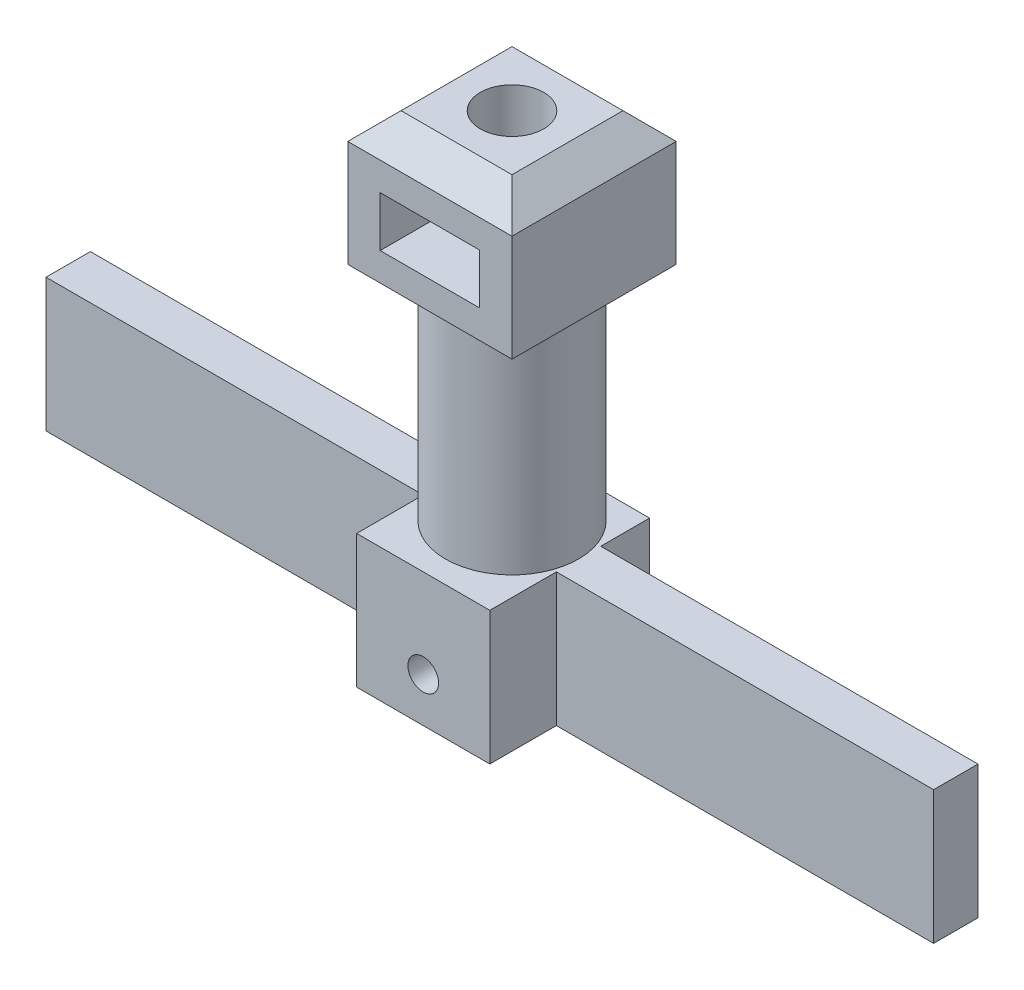
SolidWorks part; units mm, degrees
ref_plane "Front Plane" through (0, 0, 0) normal (0, 0, 1) x (1, 0, 0)
ref_plane "Top Plane" through (0, 0, 0) normal (0, 1, 0) x (1, 0, 0)
ref_plane "Right Plane" through (0, 0, 0) normal (1, 0, 0) x (0, 0, -1)
sketch "Sketch1" plane through (0, 0, 0) normal (0, 1, 0) x (1, 0, 0)
  line L1 (0, 0) -> (100, 0)
  line L2 (0, 0) -> (0, 10)
  line L3 (0, 10) -> (100, 10)
  line L4 (100, 0) -> (100, 10)
  dimension "D1" = 100
  dimension "D2" = 10
extrude "Boss-Extrude1" add sketch "Sketch1" along normal blind 15
sketch "Sketch2" plane through (0, 15, 0) normal (0, 1, 0) x (1, 0, 0)
  line L0 (100, 10) -> (0, 10) construction
  line L1 (100, 0) -> (100, 10) construction
  circle A0 centre (50, 5) radius 7.5
  dimension "D2" = 15
  dimension "D3" = 50
  dimension "D1" = 5
extrude "Boss-Extrude2" add sketch "Sketch2" along normal blind 20
sketch "Sketch3" plane through (0, 35, 0) normal (0, 1, 0) x (1, 0, 0)
  line L1 (40.75, 14.25) -> (59.25, 14.25)
  line L2 (40.75, 14.25) -> (40.75, -4.25)
  line L3 (40.75, -4.25) -> (59.25, -4.25)
  line L4 (59.25, 14.25) -> (59.25, -4.25)
  circle A0 centre (50, 5) radius 7.5 construction
  circle A1 centre (50, 5) radius 7.5 construction
  dimension "D4" = 9.25
  dimension "D1" = 18.5
  dimension "D2" = 18.5
  dimension "D3" = 9.25
extrude "Boss-Extrude3" add sketch "Sketch3" along normal blind 20
chamfer "Chamfer1" distance 3 angle 45 4 edges at (50, 55, -14.25) (59.25, 55, -5) (50, 55, 4.25) (40.75, 55, -5)
chamfer "Chamfer2" distance 5 angle 45 4 edges at (50, 35, -14.25) (40.75, 35, -5) (59.25, 35, -5) (50, 35, 4.25)
sketch "Sketch4" plane through (0, 0, 4.25) normal (0, 0, 1) x (1, 0, 0)
  line L0 (59.25, 52) -> (40.75, 52) construction
  line L1 (44.4, 48.825) -> (55.6, 48.825)
  line L2 (44.4, 48.825) -> (44.4, 43.175)
  line L3 (44.4, 43.175) -> (55.6, 43.175)
  line L4 (55.6, 48.825) -> (55.6, 43.175)
  line L5 (40.75, 40) -> (59.25, 40) construction
  line L6 (59.25, 52) -> (59.25, 40) construction
  line L7 (40.75, 52) -> (40.75, 40) construction
  dimension "D1" = 11.2
  dimension "D2" = 5.65
  dimension "D3" = 3.175
  dimension "D4" = 3.175
  dimension "D5" = 3.65
  dimension "D6" = 3.65
extrude "Cut-Extrude1" cut sketch "Sketch4" against normal through all
hole_wizard "1/4 Clearance Hole1" positions "Sketch6" profile "Sketch7" hole size "1/4" standard "ANSI Inch"
sketch "Sketch6" plane through (0, 55, 0) normal (0, 1, 0) x (1, 0, 0)
  line L0 (56.25, 11.25) -> (43.75, 11.25) construction
  line L1 (43.75, -1.25) -> (56.25, -1.25) construction
  line L2 (56.25, -1.25) -> (56.25, 11.25) construction
  point P0 (50, 5)
  dimension "D1" = 6.25
  dimension "D2" = 6.25
  dimension "D3" = 6.25
sketch "Sketch7" plane through (50, 55, -5) normal (1, 0, 0) x (0, 0, 1)
  line L0 (0, 0) -> (0, 27.1458)
  line L1 (0, 27.1458) -> (3.5712, 25)
  line L2 (3.5712, 25) -> (3.5712, 0)
  line L5 (3.5712, 0) -> (0, 0)
  line L10 (0, 27.1458) -> (-3.5712, 25) construction
  line L11 (0, -6.35) -> (0, 107.95) construction
  dimension "Hole Dia." = 7.1425
  dimension "Hole Depth" = 25
  dimension "Drill Angle" = 118
sketch "Sketch8" plane through (0, 0, 0) normal (0, 0, 1) x (1, 0, 0)
  line L0 (0, 15) -> (44.4098, 15) construction
  line L1 (42.5, 15) -> (57.5, 15)
  line L2 (42.5, 15) -> (42.5, 0)
  line L3 (42.5, 0) -> (57.5, 0)
  line L4 (57.5, 15) -> (57.5, 0)
  line L5 (0, 0) -> (100, 0) construction
  line L6 (0, 15) -> (0, 0) construction
  line L7 (100, 15) -> (100, 0) construction
  point P8 (0, 7.5)
  dimension "D1" = 15
  dimension "D2" = 42.5
  dimension "D3" = 42.5
extrude "Boss-Extrude4" add sketch "Sketch8" along normal blind 5
sketch "Sketch9" plane through (0, 0, 0) normal (0, -1, 0) x (1, 0, 0)
  circle A0 centre (50, -5) radius 2.65
  dimension "D1" = 5.3
extrude "Cut-Extrude2" cut sketch "Sketch9" against normal blind 25
hole_wizard "#4 Clearance Hole1" positions "Sketch12" profile "Sketch11" hole size "#4" standard "ANSI Inch"
sketch "Sketch12" plane through (0, 0, 5) normal (0, 0, 1) x (1, 0, 0)
  line L0 (50, 25) -> (50, 0) construction
  line L1 (42.5, 0) -> (57.5, 0) construction
  point P0 (50, 5)
  dimension "D1" = 5
sketch "Sketch11" plane through (50, 5, 5) normal (1, 0, 0) x (0, -1, 0)
  line L0 (0, 0) -> (0, 11.0378)
  line L1 (0, 11.0378) -> (1.7272, 10)
  line L2 (1.7272, 10) -> (1.7272, 0)
  line L5 (1.7272, 0) -> (0, 0)
  line L10 (0, 11.0378) -> (-1.7272, 10) construction
  line L11 (0, -6.35) -> (0, 107.95) construction
  dimension "Hole Dia." = 3.4544
  dimension "Hole Depth" = 10
  dimension "Drill Angle" = 118
sketch "Sketch13" plane through (0, 0, 0) normal (0, -1, 0) x (1, 0, 0)
  line L0 (42.5, 5) -> (57.5, 5) construction
  line L1 (46.7, 2.5) -> (53.3, 2.5)
  line L2 (46.7, 2.5) -> (46.7, -0.29)
  line L3 (46.7, -0.29) -> (53.3, -0.29)
  line L4 (53.3, 2.5) -> (53.3, -0.29)
  line L5 (50, -2.9902) -> (50, 5) construction
  dimension "D1" = 6.6
  dimension "D2" = 2.79
  dimension "D3" = 2.5
  dimension "D4" = 3.3
extrude "Cut-Extrude3" cut sketch "Sketch13" against normal blind 7.7559
sketch "Sketch14" plane through (0, 0, -10) normal (0, 0, -1) x (-1, 0, 0)
  line L1 (-57.5, 15) -> (-42.5, 15)
  line L2 (-57.5, 15) -> (-57.5, 0)
  line L3 (-57.5, 0) -> (-42.5, 0)
  line L4 (-42.5, 15) -> (-42.5, 0)
extrude "Boss-Extrude5" add sketch "Sketch14" along normal blind 3
sketch "Sketch15" plane through (100, 0, 0) normal (1, 0, 0) x (0, 0, -1)
  line L0 (0, 0) -> (10, 0) construction
  line L1 (0, 15) -> (2.5, 15)
  line L2 (0, 15) -> (0, 0)
  line L3 (0, 0) -> (2.5, 0)
  line L4 (2.5, 15) -> (2.5, 0)
  line L6 (10, 15) -> (7.5, 15)
  line L7 (10, 15) -> (10, 0)
  line L8 (10, 0) -> (7.5, 0)
  line L9 (7.5, 15) -> (7.5, 0)
  dimension "D1" = 5
  dimension "D2" = 2.5
extrude "Cut-Extrude4" cut sketch "Sketch15" against normal up to surface (42.5 mm away) up to face at (57.5, 7.5, 2.5)
sketch "Sketch16" plane through (0, 0, 0) normal (-1, 0, 0) x (0, 0, 1)
  line L0 (-10, 0) -> (0, 0) construction
  line L1 (-10, 15) -> (-7.5, 15)
  line L2 (-10, 15) -> (-10, 0)
  line L3 (-10, 0) -> (-7.5, 0)
  line L4 (-7.5, 15) -> (-7.5, 0)
  line L6 (0, 15) -> (-2.5, 15)
  line L7 (0, 15) -> (0, 0)
  line L8 (0, 0) -> (-2.5, 0)
  line L9 (-2.5, 15) -> (-2.5, 0)
  dimension "D1" = 2.5
  dimension "D2" = 5
extrude "Cut-Extrude5" cut sketch "Sketch16" against normal up to surface (42.5 mm away) up to face at (42.5, 7.5, -11.5)
equation "\"D3@Sketch3\"=\"D1@Sketch3\"*.5"
equation "\"D4@Sketch3\"=\"D3@Sketch3\""
equation "\"D4@Sketch13\"=0.5*\"D1@Sketch13\""
